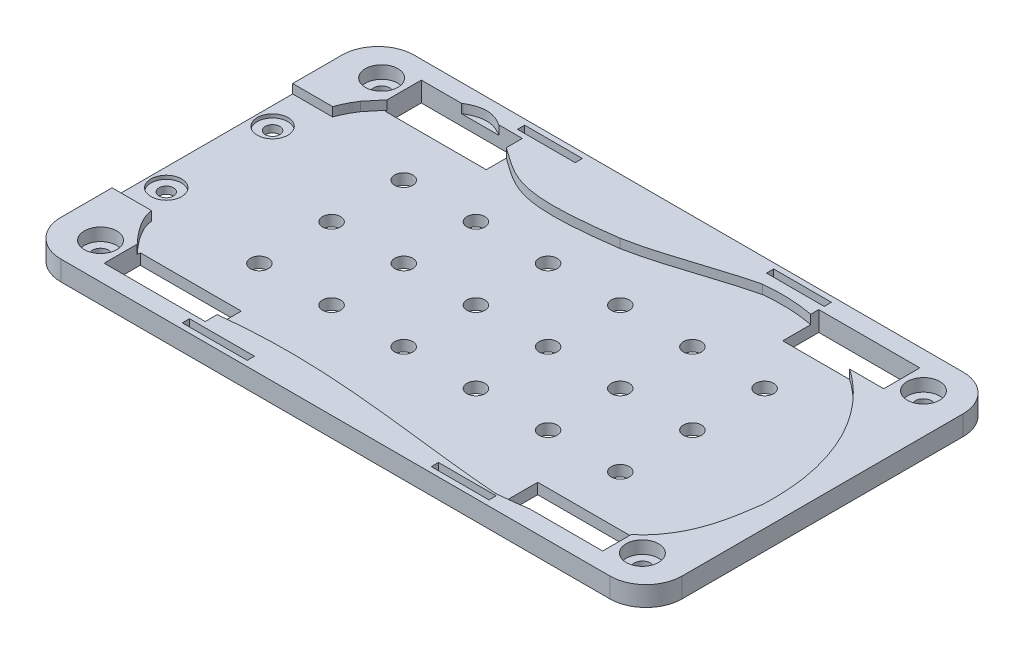
SolidWorks part; units mm, degrees
ref_plane "Front Plane" through (0, 0, 0) normal (0, 0, 1) x (1, 0, 0)
ref_plane "Top Plane" through (0, 0, 0) normal (0, 1, 0) x (1, 0, 0)
ref_plane "Right Plane" through (0, 0, 0) normal (1, 0, 0) x (0, 0, -1)
sketch "Sketch1" plane through (0, 0, 0) normal (0, 1, 0) x (1, 0, 0)
  line L1 (-78.1571, 35.933) -> (-78.1571, -14.1122)
  line L2 (78.9797, 0.0343) -> (-78.1571, 0.0343) construction
  line L3 (-77.1571, 35.7646) -> (-77.1571, -14.1122)
  line L4 (78.9797, -0.9657) -> (-78.1571, -0.9657)
  arc A1 (37.8695, -35.2975) -> (39.5975, -35.2134) centre (38.2635, -25.6055) ccw
  arc A2 (37.9263, -34.299) -> (39.4753, -34.2207) centre (38.2635, -25.6055) ccw
  spline S0 degree 1 poles (-77.1571, -14.1122) (-56.919, -31.9168) knots 0 0 1 1 construction
  spline S1 degree 1 poles (-56.919, -31.9168) (37.9263, -34.299) knots 0 0 1 1 construction
  spline S2 degree 1 poles (39.4753, -34.2207) (77.9849, 0.1477) knots 0 0 1 1 construction
  spline S3 degree 1 poles (77.9849, 0.1477) (25.0602, 52.8732) knots 0 0 1 1 construction
  spline S4 degree 1 poles (25.0602, 52.8732) (-5.6593, 44.1904) knots 0 0 1 1 construction
  spline S5 degree 1 poles (-5.6593, 44.1904) (-43.9853, 50.6886) knots 0 0 1 1 construction
  spline S6 degree 1 poles (-43.9853, 50.6886) (-59.7702, 54.7238) knots 0 0 1 1 construction
  spline S7 degree 1 poles (-59.7702, 54.7238) (-74.5158, 41.0521) knots 0 0 1 1 construction
  spline S8 degree 1 poles (-74.5158, 41.0521) (-77.1571, 35.7646) knots 0 0 1 1 construction
  spline S9 degree 3 poles (-77.1571, -14.1122) (-77.1565, -14.3701) (-77.1092, -14.8732) (-76.8359, -15.9559) (-76.1879, -17.5008) (-75.044, -19.4183) (-73.152, -22.0092) (-70.3495, -25.0822) (-66.8736, -28.0972) (-63.6864, -30.2141) (-61.0019, -31.4062) (-58.8274, -31.848) (-57.5718, -31.8794) (-56.919, -31.9168) knots 0.000484 0.000484 0.000484 0.000484 0.031521 0.062558 0.124632 0.186706 0.248781 0.372929 0.497077 0.621225 0.745373 0.869521 0.993669 0.993669 0.993669 0.993669
  spline S10 degree 3 poles (-56.919, -31.9168) (-56.6769, -31.8873) (-56.2021, -31.8274) (-55.1791, -31.687) (-53.8294, -31.4877) (-52.0759, -31.2184) (-49.5744, -30.8354) (-46.1465, -30.3372) (-41.5825, -29.7813) (-36.5976, -29.3261) (-29.4274, -28.913) (-19.5571, -28.8468) (-6.4839, -29.5875) (5.2448, -30.7865) (15.023, -31.9295) (22.521, -32.809) (30.1538, -33.642) (35.3408, -34.1075) (37.9263, -34.299) knots 0.000538 0.000538 0.000538 0.000538 0.016152 0.031766 0.062993 0.094221 0.125449 0.187904 0.250359 0.312815 0.37527 0.50018 0.625091 0.750001 0.812457 0.874912 0.937367 0.999822 0.999822 0.999822 0.999822
  spline S11 degree 3 poles (39.4753, -34.2207) (41.0079, -34.0574) (44.09, -33.7147) (50.0835, -32.8429) (57.0969, -31.1859) (64.2184, -27.8839) (69.7763, -23.1857) (73.0497, -18.2789) (74.9177, -14.0269) (75.9805, -10.7732) (76.7509, -7.5724) (77.1995, -5.064) (77.4798, -3.2279) (77.6607, -1.9649) (77.8261, -0.8108) (77.9301, -0.1834) (77.9849, 0.1477) knots -0.000309 -0.000309 -0.000309 -0.000309 0.063093 0.126495 0.253299 0.380104 0.506908 0.633712 0.697114 0.760516 0.823918 0.88732 0.919021 0.950722 0.982423 1.014124 1.014124 1.014124 1.014124
  spline S12 degree 3 poles (77.9849, 0.1477) (78.0286, 1.2633) (78.0637, 3.5224) (77.9426, 6.757) (77.6596, 9.9047) (77.0733, 13.9671) (75.9626, 18.7836) (73.4433, 25.9357) (69.0206, 33.8098) (62.0495, 41.4932) (53.7895, 47.3444) (44.6121, 51.2947) (34.9036, 53.2804) (28.3113, 53.2357) (25.0602, 52.8732) knots 0.000169 0.000169 0.000169 0.000169 0.031414 0.062658 0.093902 0.125147 0.187635 0.250124 0.375101 0.500079 0.625056 0.750034 0.875011 0.999988 0.999988 0.999988 0.999988
  spline S13 degree 3 poles (25.0602, 52.8732) (19.8954, 51.6294) (12.3224, 49.1317) (2.1607, 45.9713) (-3.0371, 44.6913) (-5.6593, 44.1904) knots 0.000659 0.000659 0.000659 0.000659 0.498067 0.746772 0.995476 0.995476 0.995476 0.995476
  spline S14 degree 3 poles (-5.6593, 44.1904) (-6.6879, 44.0461) (-8.7287, 43.7719) (-12.9633, 43.2668) (-18.1826, 42.7952) (-23.9015, 42.6322) (-28.8306, 42.9899) (-32.9666, 43.9514) (-35.9177, 45.2914) (-38.1959, 46.6779) (-39.9392, 47.8658) (-41.507, 48.9798) (-42.8638, 49.9292) (-43.6163, 50.4405) (-43.9853, 50.6886) knots -0.000196 -0.000196 -0.000196 -0.000196 0.062587 0.12537 0.250936 0.376501 0.502067 0.627632 0.753198 0.815981 0.878764 0.941546 0.972938 1.004329 1.004329 1.004329 1.004329
  spline S15 degree 3 poles (-43.9853, 50.6886) (-44.2445, 50.8673) (-44.7682, 51.2325) (-45.7507, 51.9331) (-46.8912, 52.7591) (-48.146, 53.6496) (-49.6971, 54.6811) (-51.4608, 55.6487) (-53.4077, 56.2593) (-55.2517, 56.3574) (-56.711, 56.0808) (-57.7948, 55.7138) (-58.5465, 55.3915) (-59.2299, 55.0428) (-59.5837, 54.8359) (-59.7702, 54.7238) knots -0.002497 -0.002497 -0.002497 -0.002497 0.029066 0.060629 0.123754 0.18688 0.250006 0.376257 0.502509 0.62876 0.755012 0.818137 0.881263 0.944389 1.007515 1.007515 1.007515 1.007515
  spline S16 degree 3 poles (-78.1571, -14.1122) (-78.1559, -14.7524) (-77.9173, -15.9777) (-77.0678, -17.9828) (-75.8538, -20.0098) (-73.8827, -22.6985) (-70.9901, -25.8584) (-67.4096, -28.9504) (-64.0991, -31.1349) (-61.2379, -32.3904) (-59.243, -32.7789) (-57.8421, -32.8756) (-57.2118, -32.9007) (-56.8882, -32.9203) knots 0.000409 0.000409 0.000409 0.000409 0.062843 0.125276 0.18771 0.250143 0.375011 0.499878 0.624745 0.749612 0.874479 0.936913 0.999346 0.999346 0.999346 0.999346
  spline S17 degree 3 poles (-56.8882, -32.9203) (-56.6427, -32.8908) (-56.1603, -32.8306) (-55.1309, -32.6904) (-53.7754, -32.491) (-52.0233, -32.2221) (-49.5292, -31.8398) (-46.1189, -31.3427) (-41.5829, -30.7872) (-36.6286, -30.3313) (-29.4997, -29.9158) (-19.6749, -29.8441) (-6.6369, -30.5782) (5.0856, -31.7749) (14.8757, -32.919) (22.3927, -33.8009) (30.0532, -34.6371) (35.2704, -35.1052) (37.8695, -35.2975) knots -0.001373 -0.001373 -0.001373 -0.001373 0.014273 0.029919 0.06121 0.092502 0.123794 0.186377 0.24896 0.311543 0.374127 0.499293 0.62446 0.749626 0.81221 0.874793 0.937376 0.99996 0.99996 0.99996 0.99996
  spline S18 degree 3 poles (39.5975, -35.2134) (41.1398, -35.049) (44.2356, -34.7045) (50.3018, -33.8209) (57.4502, -32.1301) (64.7991, -28.7164) (70.5782, -23.8111) (73.9656, -18.7006) (75.8832, -14.3057) (76.9672, -10.962) (77.7479, -7.6914) (78.1997, -5.145) (78.4804, -3.2966) (78.6613, -2.0308) (78.824, -0.9009) (78.9276, -0.2806) (78.9816, 0.0458) knots -0.000086 -0.000086 -0.000086 -0.000086 0.063428 0.126941 0.253967 0.380993 0.50802 0.635046 0.698559 0.762072 0.825585 0.889098 0.920855 0.952612 0.984368 1.016125 1.016125 1.016125 1.016125
  spline S19 degree 3 poles (78.9816, 0.0458) (79.0271, 1.1797) (79.0647, 3.4739) (78.9444, 6.7697) (78.6587, 9.9749) (78.0642, 14.1169) (76.9341, 19.0326) (74.3646, 26.3398) (69.8439, 34.3944) (62.712, 42.2543) (54.2626, 48.2351) (44.8799, 52.2671) (34.9529, 54.2886) (28.2109, 54.2351) (24.8869, 53.8601) knots -0.000407 -0.000407 -0.000407 -0.000407 0.03088 0.062166 0.093453 0.12474 0.187314 0.249888 0.375035 0.500183 0.62533 0.750478 0.875625 1.000773 1.000773 1.000773 1.000773
  spline S20 degree 3 poles (24.8869, 53.8601) (22.2839, 53.2349) (17.1223, 51.77) (6.9788, 48.4835) (-0.6206, 46.1711) (-5.8226, 45.1772) knots -0.001281 -0.001281 -0.001281 -0.001281 0.247714 0.49671 0.9947 0.9947 0.9947 0.9947
  spline S21 degree 3 poles (-5.8226, 45.1772) (-6.8463, 45.0337) (-8.8779, 44.761) (-13.0882, 44.2593) (-18.2643, 43.7927) (-23.9018, 43.6338) (-28.7026, 43.9859) (-32.6523, 44.9085) (-35.4477, 46.177) (-37.6484, 47.5152) (-39.3619, 48.6824) (-40.9248, 49.793) (-42.292, 50.7496) (-43.0505, 51.2651) (-43.4225, 51.5151) knots 0.000305 0.000305 0.000305 0.000305 0.063048 0.125791 0.251276 0.376761 0.502247 0.627732 0.753218 0.815961 0.878703 0.941446 0.972817 1.004189 1.004189 1.004189 1.004189
  spline S22 degree 3 poles (-43.4225, 51.5151) (-43.6786, 51.6918) (-44.1958, 52.0526) (-45.1684, 52.7462) (-46.308, 53.5714) (-47.577, 54.4721) (-49.1727, 55.5335) (-51.0441, 56.5648) (-53.2147, 57.2519) (-55.3195, 57.3652) (-56.9568, 57.0533) (-58.1477, 56.6506) (-58.9689, 56.2985) (-59.5708, 55.992) (-60.0059, 55.7483) (-60.1862, 55.6406) (-60.2803, 55.5839) knots -0.002294 -0.002294 -0.002294 -0.002294 0.029245 0.060783 0.12386 0.186936 0.250013 0.376167 0.50232 0.628473 0.754627 0.817704 0.88078 0.943857 0.975396 1.006934 1.006934 1.006934 1.006934
  spline S23 degree 3 poles (-60.2803, 55.5839) (-60.715, 55.3297) (-61.582, 54.801) (-63.2222, 53.7187) (-65.9105, 51.7373) (-69.2431, 48.741) (-72.0244, 45.6929) (-73.7392, 43.6279) (-74.6657, 42.4756) (-75.1049, 41.9202) (-75.3265, 41.639) knots 0.000427 0.000427 0.000427 0.000427 0.063268 0.126109 0.251792 0.503158 0.754524 0.880206 0.943048 1.005889 1.005889 1.005889 1.005889
  spline S24 degree 3 poles (-59.7702, 54.7238) (-60.1936, 54.4761) (-61.0386, 53.9612) (-62.6368, 52.9072) (-65.2587, 50.9763) (-68.5171, 48.0498) (-71.2443, 45.0657) (-73.1899, 42.7247) (-74.0698, 41.6179) (-74.5158, 41.0521) knots 0.000174 0.000174 0.000174 0.000174 0.062881 0.125589 0.251004 0.501833 0.752662 0.878077 1.003492 1.003492 1.003492 1.003492
  spline S25 degree 3 poles (-74.5158, 41.0521) (-75.0658, 40.2217) (-76.0765, 38.4779) (-76.8336, 36.6875) (-77.1571, 35.7646) knots 0.499549 0.499549 0.499549 0.499549 0.499766 0.499983 0.499983 0.499983 0.499983
  spline S26 degree 3 poles (-75.3265, 41.639) (-75.92, 40.746) (-77.0064, 38.8701) (-77.815, 36.9314) (-78.1571, 35.933) knots 0.499546 0.499546 0.499546 0.499546 0.49977 0.499995 0.499995 0.499995 0.499995
  point P0 (0.4631, 0.0343)
  dimension "D1" = 1
sketch "Sketch6" plane through (0, 0, 0) normal (0, 1, 0) x (1, 0, 0)
  line L0 (-78.1571, 35.933) -> (-78.1571, -14.1122) construction
  line L1 (73.9816, 59.5839) -> (-78.1571, 59.5839)
  line L2 (83.9816, 49.5839) -> (83.9816, -28.2975)
  line L3 (73.9816, -38.2975) -> (-78.1571, -38.2975)
  line L4 (-88.1571, 49.5839) -> (-88.1571, -28.2975)
  arc A0 (-78.1571, -38.2975) -> (-88.1571, -28.2975) centre (-78.1571, -28.2975) cw
  arc A1 (-88.1571, 49.5839) -> (-78.1571, 59.5839) centre (-78.1571, 49.5839) cw
  arc A2 (73.9816, 59.5839) -> (83.9816, 49.5839) centre (73.9816, 49.5839) cw
  arc A3 (83.9816, -28.2975) -> (73.9816, -38.2975) centre (73.9816, -28.2975) cw
  dimension "D5" = 10
  dimension "D1" = 5
  dimension "D2" = 10
  dimension "D3" = 3
  dimension "D4" = 4
extrude "Boss-Extrude2" add sketch "Sketch6" along normal blind 6.5
extrude "Cut-Extrude1" cut sketch "Sketch1" along normal blind 2.5 contours A2 S11 L4 L3 S9 S10 | S24 S25 L3 L4 S11 S12 S13 S14 S15 region at (0.1139, 0, 15.5782) region at (-2.2602, 0, -23.2786)
sketch "Sketch7" plane through (0, 0, 0) normal (0, -1, 0) x (1, 0, 0)
  line L1 (-76.2189, 14.1122) -> (-91.3452, 14.1122)
  line L2 (-76.2189, 14.1122) -> (-76.2189, -35.933)
  line L3 (-76.2189, -35.933) -> (-91.3452, -35.933)
  line L4 (-91.3452, 14.1122) -> (-91.3452, -35.933)
extrude "Cut-Extrude2" cut sketch "Sketch7" against normal up to surface (2.5 mm away) contours L2 L1 L4 L3 up to face at (-19.4492, 2.5, -12.7234)
sketch "Sketch8" plane through (0, 6.5, 0) normal (0, 1, 0) x (1, 0, 0)
  line L0 (83.9816, 10.6432) -> (-88.1571, 10.6432) construction
  line L1 (83.9816, -28.2975) -> (83.9816, 49.5839) construction
  line L2 (-88.1571, 49.5839) -> (-88.1571, -28.2975) construction
  line L3 (-2.0877, 59.5839) -> (-2.0877, -38.2975) construction
  line L4 (73.9816, 59.5839) -> (-78.1571, 59.5839) construction
  line L5 (-78.1571, -38.2975) -> (73.9816, -38.2975) construction
  line L7 (78.9816, 54.5839) -> (38.9816, 54.5839)
  line L8 (78.9816, 54.5839) -> (78.9816, 44.5839)
  line L9 (78.9816, 44.5839) -> (38.9816, 44.5839)
  line L10 (38.9816, 54.5839) -> (38.9816, 44.5839)
  line L22 (38.9816, 49.5839) -> (78.9816, 49.5839) construction
  line L23 (66.9816, 54.5839) -> (66.9816, 44.5839)
  circle A1 centre (72.9816, 49.5839) radius 3.5
  dimension "D6" = 7
  dimension "D1" = 10
  dimension "D2" = 40
  dimension "D3" = 5
  dimension "D4" = 5
  dimension "D5" = 6
  dimension "D7" = 6
sketch "Sketch9" plane through (0, 0, 0) normal (0, -1, 0) x (1, 0, 0)
  circle A0 centre (72.9816, -49.5839) radius 4.5
  dimension "D1" = 9
extrude "Cut-Extrude5" cut sketch "Sketch9" against normal blind 3.5
sketch "Sketch10" plane through (0, 3.5, 0) normal (0, -1, 0) x (1, 0, 0)
  circle A0 centre (72.9816, -49.5839) radius 2.25
  dimension "D1" = 4.5
extrude "Cut-Extrude6" cut sketch "Sketch10" against normal blind 21
extrude "Cut-Extrude8" cut sketch "Sketch8" against normal blind 42 contours L23 L7 L10 L9 region at (52.9816, 6.5, -49.5839)
extrude "Cut-Extrude9" cut sketch "Sketch8<3>" against normal blind 1 contours L7 L23 L9 L8 A1 region at (78.8254, 6.5, -49.5839)
sketch "Sketch8<3>" plane through (0, 6.5, 0) normal (0, 1, 0) x (1, 0, 0) same geometry as "Sketch8"
sketch "Sketch12" plane through (0, 6.5, 0) normal (0, 1, 0) x (1, 0, 0)
  line L0 (-88.1571, 10.6432) -> (83.9816, 10.6432) construction
  line L1 (-88.1571, 49.5839) -> (-88.1571, -28.2975) construction
  line L2 (83.9816, -28.2975) -> (83.9816, 49.5839) construction
  line L3 (-2.0877, 59.5839) -> (-2.0877, -36.8461) construction
  line L4 (73.9816, 59.5839) -> (-78.1571, 59.5839) construction
ref_plane "Plane1" through (0, 0, -10.6432) normal (0, 0, 1) x (1, 0, 0)
ref_plane "Plane2" through (-2.0877, 0, 0) normal (-1, 0, 0) x (0, 0, 1)
mirror "Mirror1" about plane through (0, 0, -10.6432) normal (0, 0, 1) of "Cut-Extrude5", "Cut-Extrude6", "Cut-Extrude8", "Cut-Extrude9"
mirror "Mirror2" about plane through (-2.0877, 0, 0) normal (-1, 0, 0) of "Mirror1", "Cut-Extrude9", "Cut-Extrude8", "Cut-Extrude6", "Cut-Extrude5"
sketch "Sketch13" plane through (0, 6.5, 0) normal (0, 1, 0) x (1, 0, 0)
  line L0 (-83.1571, 44.5839) -> (-43.1571, 44.5839) construction
  line L1 (58.9816, 39.5839) -> (-63.1571, 39.5839)
  line L2 (58.9816, 39.5839) -> (58.9816, -18.2975)
  line L3 (58.9816, -18.2975) -> (-63.1571, -18.2975)
  line L4 (-63.1571, 39.5839) -> (-63.1571, -18.2975)
  line L5 (58.9816, 39.5839) -> (-63.1571, -18.2975) construction
  line L6 (58.9816, -18.2975) -> (-63.1571, 39.5839) construction
  line L7 (-83.1571, -23.2975) -> (-43.1571, -23.2975) construction
  line L8 (83.9816, -28.2975) -> (83.9816, 49.5839) construction
  line L9 (-88.1571, 49.5839) -> (-88.1571, -28.2975) construction
  point P0 (-2.0877, 10.6432)
  dimension "D1" = 5
  dimension "D2" = 5
  dimension "D3" = 25
  dimension "D4" = 25
extrude "Cut-Extrude10" cut sketch "Sketch13" against normal blind 1
sketch "Sketch14" plane through (0, 5.5, 0) normal (0, 1, 0) x (1, 0, 0)
  line L0 (-63.1571, 10.6432) -> (58.9816, 10.6432) construction
  line L1 (-63.1571, 39.5839) -> (-63.1571, -18.2975) construction
  line L2 (58.9816, -18.2975) -> (58.9816, 39.5839) construction
  line L3 (-63.1571, -9.3568) -> (58.9816, -9.3568) construction
  line L4 (-63.1571, 10.6432) -> (58.9816, 10.6432) construction
  line L5 (-63.1571, 30.6432) -> (58.9816, 30.6432) construction
  circle A1 centre (-12.0877, 10.6432) radius 2.5
  circle A2 centre (-32.0877, 10.6432) radius 2.5
  circle A3 centre (-52.0877, 10.6432) radius 2.5
  circle A4 centre (-12.0877, 10.6432) radius 2.5
  circle A5 centre (-32.0877, 10.6432) radius 2.5
  circle A6 centre (7.9123, 10.6432) radius 2.5
  circle A7 centre (-12.0877, 10.6432) radius 2.5
  circle A8 centre (27.9123, 10.6432) radius 2.5
  circle A9 centre (7.9123, 10.6432) radius 2.5
  circle A10 centre (7.9123, 10.6432) radius 2.5
  circle A11 centre (27.9123, 10.6432) radius 2.5
  circle A12 centre (47.9123, 10.6432) radius 2.5
  circle A13 centre (-12.0877, -9.3568) radius 2.5
  circle A14 centre (-32.0877, -9.3568) radius 2.5
  circle A15 centre (-52.0877, -9.3568) radius 2.5
  circle A16 centre (-12.0877, -9.3568) radius 2.5
  circle A17 centre (-32.0877, -9.3568) radius 2.5
  circle A18 centre (7.9123, -9.3568) radius 2.5
  circle A19 centre (-12.0877, -9.3568) radius 2.5
  circle A20 centre (27.9123, -9.3568) radius 2.5
  circle A21 centre (7.9123, -9.3568) radius 2.5
  circle A22 centre (7.9123, -9.3568) radius 2.5
  circle A23 centre (27.9123, -9.3568) radius 2.5
  circle A24 centre (47.9123, -9.3568) radius 2.5
  circle A25 centre (-12.0877, 10.6432) radius 2.5
  circle A26 centre (-32.0877, 10.6432) radius 2.5
  circle A27 centre (-52.0877, 10.6432) radius 2.5
  circle A28 centre (-12.0877, 10.6432) radius 2.5
  circle A29 centre (-32.0877, 10.6432) radius 2.5
  circle A30 centre (7.9123, 10.6432) radius 2.5
  circle A31 centre (-12.0877, 10.6432) radius 2.5
  circle A32 centre (27.9123, 10.6432) radius 2.5
  circle A33 centre (7.9123, 10.6432) radius 2.5
  circle A34 centre (7.9123, 10.6432) radius 2.5
  circle A35 centre (27.9123, 10.6432) radius 2.5
  circle A36 centre (47.9123, 10.6432) radius 2.5
  circle A37 centre (-12.0877, 30.6432) radius 2.5
  circle A38 centre (-32.0877, 30.6432) radius 2.5
  circle A39 centre (-52.0877, 30.6432) radius 2.5
  circle A40 centre (-12.0877, 30.6432) radius 2.5
  circle A41 centre (-32.0877, 30.6432) radius 2.5
  circle A42 centre (7.9123, 30.6432) radius 2.5
  circle A43 centre (-12.0877, 30.6432) radius 2.5
  circle A44 centre (27.9123, 30.6432) radius 2.5
  circle A45 centre (7.9123, 30.6432) radius 2.5
  circle A46 centre (7.9123, 30.6432) radius 2.5
  circle A47 centre (27.9123, 30.6432) radius 2.5
  circle A48 centre (47.9123, 30.6432) radius 2.5
  point P8 (-2.0877, 10.6432)
  point P37 (-2.0877, -9.3568)
  point P64 (-2.0877, 10.6432)
  point P91 (-2.0877, 30.6432)
  dimension "D2" = 5
  dimension "D1" = 10
  dimension "D3" = 3
  dimension "D4" = 4
  dimension "D5" = 2
  dimension "D6" = 2
extrude "Cut-Extrude11" cut sketch "Sketch14" against normal blind 57 contours A39 | A42 | A44 | A48 | A12 | A6 | A1 | A2 | A3 | A24 | A20 | A18 | A13 | A14 | A15 | A38 | A37 | A8 region at (-12.0877, 5.5, -10.6432) region at (-32.0877, 5.5, -10.6432) region at (-52.0877, 5.5, -10.6432) region at (7.9123, 5.5, -10.6432) region at (47.9123, 5.5, -10.6432) region at (-12.0877, 5.5, 9.3568) region at (-32.0877, 5.5, 9.3568) region at (-52.0877, 5.5, 9.3568) region at (7.9123, 5.5, 9.3568) region at (27.9123, 5.5, 9.3568) region at (47.9123, 5.5, 9.3568) region at (-52.0877, 5.5, -30.6432) region at (7.9123, 5.5, -30.6432) region at (27.9123, 5.5, -30.6432) region at (47.9123, 5.5, -30.6432)
sketch "Sketch16" plane through (0, 0, 0) normal (0, -1, 0) x (1, 0, 0)
  line L0 (78.9816, -0.5458) -> (78.9816, -79.1994) construction
  line L1 (22.9816, -56.0839) -> (-37.6427, -56.0839) construction
  line L2 (73.9816, -59.5839) -> (-78.1571, -59.5839) construction
  line L3 (38.9816, -54.3238) -> (38.9816, 38.2975) construction
  line L4 (38.9816, -59.5839) -> (38.9816, -54.3238) construction
  line L5 (38.9816, -56.0839) -> (22.9816, -56.0839)
  line L6 (38.9816, -56.0839) -> (38.9816, -58.0839)
  line L7 (38.9816, -58.0839) -> (22.9816, -58.0839)
  line L8 (22.9816, -56.0839) -> (22.9816, -58.0839)
  line L9 (-78.1571, 38.2975) -> (73.9816, 38.2975) construction
  line L10 (22.9816, -56.0839) -> (22.9816, 38.2975) construction
  line L12 (38.9816, 36.7975) -> (22.9816, 36.7975)
  line L13 (38.9816, 36.7975) -> (38.9816, 34.7975)
  line L14 (38.9816, 34.7975) -> (22.9816, 34.7975)
  line L15 (22.9816, 36.7975) -> (22.9816, 34.7975)
  line L16 (22.9816, 34.7975) -> (-46.0184, 34.7975) construction
  line L17 (-30.0184, -56.0839) -> (-46.0184, -56.0839)
  line L18 (-30.0184, -56.0839) -> (-30.0184, -58.0839)
  line L19 (-30.0184, -58.0839) -> (-46.0184, -58.0839)
  line L20 (-46.0184, -56.0839) -> (-46.0184, -58.0839)
  line L22 (-28.0184, 34.7975) -> (-46.0184, 34.7975)
  line L23 (-28.0184, 34.7975) -> (-28.0184, 36.7975)
  line L24 (-28.0184, 36.7975) -> (-46.0184, 36.7975)
  line L25 (-46.0184, 34.7975) -> (-46.0184, 36.7975)
  dimension "D1" = 40
  dimension "D2" = 16
  dimension "D3" = 1.5
  dimension "D4" = 2
  dimension "D5" = 2
  dimension "D6" = 1.5
  dimension "D7" = 125
  dimension "D8" = 16
  dimension "D9" = 2
  dimension "D10" = 18
  dimension "D11" = 2
extrude "Cut-Extrude12" cut sketch "Sketch16" against normal blind 57
sketch "Sketch17" plane through (0, 5.5, 0) normal (0, 1, 0) x (1, 0, 0)
  line L1 (-99.5963, 69.0247) -> (98.4238, 69.0247)
  line L2 (-99.5963, 69.0247) -> (-99.5963, -53.2143)
  line L3 (-99.5963, -53.2143) -> (98.4238, -53.2143)
  line L4 (98.4238, 69.0247) -> (98.4238, -53.2143)
extrude "Cut-Extrude14" cut sketch "Sketch17" along normal blind 48.5
sketch "Sketch23" plane through (0, 2.5, 0) normal (0, -1, 0) x (1, 0, 0)
  line L0 (-88.1571, -10.9104) -> (-64.7808, -10.9104) construction
  line L1 (-88.1571, -35.933) -> (-88.1571, 14.1122) construction
  circle A0 centre (-83.1571, 4.0896) radius 2
  circle A1 centre (-83.1571, 4.0896) radius 4.25
  dimension "D1" = 4
  dimension "D4" = 8.5
  dimension "D2" = 15
  dimension "D3" = 5
extrude "Cut-Extrude15" cut sketch "Sketch23" against normal blind 48.5 contours A0
extrude "Cut-Extrude16" cut sketch "Sketch23<3>" against normal blind 1
sketch "Sketch23<3>" plane through (0, 2.5, 0) normal (0, -1, 0) x (1, 0, 0) same geometry as "Sketch23"
mirror "Mirror4" about plane through (0, 0, -10.6432) normal (0, 0, 1) of "Cut-Extrude16", "Cut-Extrude15"
sketch "Sketch24" plane through (0, 5.5, 0) normal (0, 1, 0) x (1, 0, 0)
  circle A0 centre (-77.1571, 49.5839) radius 3.25
  circle A1 centre (-77.1571, 49.5839) radius 2.25
  circle A2 centre (72.9816, 49.5839) radius 2.25
  circle A3 centre (72.9816, 49.5839) radius 3.25
  circle A4 centre (72.9816, -28.2975) radius 2.25
  circle A5 centre (-77.1571, -28.2975) radius 2.25
  circle A6 centre (-77.1571, -28.2975) radius 3.25
  circle A7 centre (72.9816, -28.2975) radius 3.25
  dimension "D1" = 6.5
  dimension "D2" = 6.5
  dimension "D3" = 6.5
  dimension "D4" = 6.5
extrude "Boss-Extrude3" add sketch "Sketch24" along normal blind 1
ref_plane "Plane3" through (0, 0, 0) normal (0, -1, 0) x (-1, 0, 0)
mirror "Mirror5" about plane through (0, 0, 0) normal (0, -1, 0) of "Boss-Extrude3", "Mirror4", "Cut-Extrude16", "Cut-Extrude15", "Cut-Extrude14", "Cut-Extrude12", "Cut-Extrude11", "Cut-Extrude10", "Mirror2", "Mirror1", "Cut-Extrude9", "Cut-Extrude8", "Cut-Extrude6", "Cut-Extrude5", "Cut-Extrude2", "Cut-Extrude1", "Boss-Extrude2"
sketch "Sketch25" plane through (0, 5.5, 0) normal (0, 1, 0) x (1, 0, 0)
  line L1 (-109.2871, 73.7066) -> (111.0455, 73.7066)
  line L2 (-109.2871, 73.7066) -> (-109.2871, -75.7235)
  line L3 (-109.2871, -75.7235) -> (111.0455, -75.7235)
  line L4 (111.0455, 73.7066) -> (111.0455, -75.7235)
extrude "Cut-Extrude18" cut sketch "Sketch25" against normal up to surface (5.5 mm away) and the other way blind 10 contours L2 L1 L4 L3 up to plane "Plane3"
ref_plane "Plane4" through (-77.0974, 0, 0) normal (-1, 0, 0) x (0, 0, 1)
ref_plane "Plane6" through (0, 0, -35.933) normal (0, 0, 1) x (1, 0, 0)
